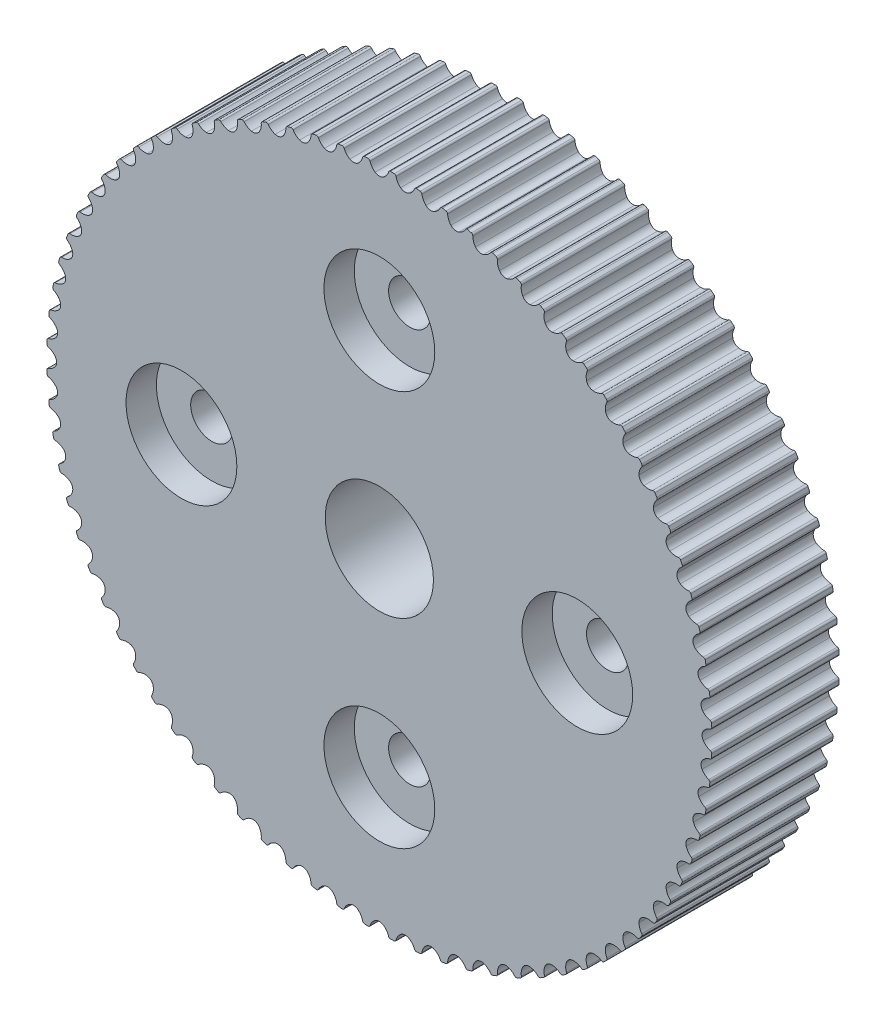
SolidWorks part; units mm, degrees
ref_plane "Front Plane" through (0, 0, 0) normal (0, 0, 1) x (1, 0, 0)
ref_plane "Top Plane" through (0, 0, 0) normal (0, 1, 0) x (1, 0, 0)
ref_plane "Right Plane" through (0, 0, 0) normal (1, 0, 0) x (0, 0, -1)
sketch "Sketch1" plane through (0, 0, 0) normal (0, 0, 1) x (1, 0, 0)
  line L3 (0, 25.2095) -> (1.9984, 25.1302) construction
  line L4 (0, 0) -> (0, 24.4595) construction
  line L5 (0, 24.4595) -> (0, 25.741) construction
  line L15 (1.9984, 25.1302) -> (2.047, 25.741)
  line L16 (2.047, 25.741) -> (-2.047, 25.741)
  line L17 (0, 24.4595) -> (0.1538, 24.4595) construction
  line L18 (-1.9984, 25.1302) -> (-2.047, 25.741)
  circle A0 centre (0, 0) radius 25.4635 construction
  circle A1 centre (0, 0) radius 25.2095 construction
  circle A2 centre (0, 0) radius 24.9555 construction
  arc A10 (0.8513, 25.1951) -> (1.9984, 25.1302) centre (0, 0) cw
  arc A11 (-0.3168, 24.5588) -> (0.3168, 24.5588) centre (0, 25.0145) ccw
  arc A12 (0.3168, 24.5588) -> (0.7027, 25.0889) centre (-0.254, 25.3799) ccw
  arc A13 (0.7027, 25.0889) -> (0.8513, 25.1951) centre (0.8462, 25.0452) cw
  arc A14 (-0.8513, 25.1951) -> (-1.9984, 25.1302) centre (0, 0) ccw
  arc A15 (-0.7027, 25.0889) -> (-0.8513, 25.1951) centre (-0.8462, 25.0452) ccw
  arc A16 (-0.3168, 24.5588) -> (-0.7027, 25.0889) centre (0.254, 25.3799) cw
  point P11 (0, 25.4635)
  point P13 (0, 25.2095)
  point P14 (0, 24.9555)
  dimension "D2" = 0.2775
sketch "Sketch2" plane through (0, 0, 0) normal (1, 0, 0) x (0, 0, -1)
  line L0 (-9.525, 4.1) -> (9.525, 4.1)
  line L1 (-9.525, 4.1) -> (-9.525, 19.05)
  line L2 (-9.525, 19.05) -> (-0.125, 19.05)
  line L3 (-0.125, 19.05) -> (-0.125, 25.2095)
  line L9 (9.525, 25.2095) -> (9.525, 4.1)
  line L10 (-9.525, 0) -> (9.525, 0) construction
  line L16 (-0.125, 25.2095) -> (9.525, 25.2095)
  point P25 (9.525, 0)
  point P26 (-0.125, 0)
  dimension "OA" = 19.05
  dimension "Bore" = 8.2
  dimension "Hub Dia" = 38.1
  dimension "Outside Width" = 9.65
revolve "Revolve1" add sketch "Sketch2" angle 360 mid plane about L10
sketch "Sketch3" plane through (0, 0, 0) normal (0, 0, 1) x (1, 0, 0)
  line L3 (1.9984, 25.1302) -> (2.047, 25.741) construction
  line L4 (-1.9984, 25.1302) -> (-2.047, 25.741) construction
  line L5 (2.047, 25.741) -> (-2.047, 25.741) construction
  line L6 (1.9984, 25.1302) -> (2.047, 25.741)
  line L7 (-1.9984, 25.1302) -> (-2.047, 25.741)
  line L8 (2.047, 25.741) -> (-2.047, 25.741)
  arc A0 (1.9984, 25.1302) -> (0.8513, 25.1951) centre (0, 0) ccw construction
  arc A1 (0.8513, 25.1951) -> (0.7027, 25.0889) centre (0.8462, 25.0452) ccw construction
  arc A3 (0.3168, 24.5588) -> (0.7027, 25.0889) centre (-0.254, 25.3799) ccw construction
  arc A4 (-0.3168, 24.5588) -> (0.3168, 24.5588) centre (0, 25.0145) ccw construction
  arc A5 (-0.7027, 25.0889) -> (-0.3168, 24.5588) centre (0.254, 25.3799) ccw construction
  arc A6 (-0.7027, 25.0889) -> (-0.8513, 25.1951) centre (-0.8462, 25.0452) ccw construction
  arc A7 (-0.8513, 25.1951) -> (-1.9984, 25.1302) centre (0, 0) ccw construction
  arc A8 (1.9984, 25.1302) -> (0.8513, 25.1951) centre (0, 0) ccw
  arc A9 (0.8513, 25.1951) -> (0.7027, 25.0889) centre (0.8462, 25.0452) ccw
  arc A10 (0.3168, 24.5588) -> (0.7027, 25.0889) centre (-0.254, 25.3799) ccw
  arc A11 (-0.3168, 24.5588) -> (0.3168, 24.5588) centre (0, 25.0145) ccw
  arc A12 (-0.7027, 25.0889) -> (-0.3168, 24.5588) centre (0.254, 25.3799) ccw
  arc A13 (-0.7027, 25.0889) -> (-0.8513, 25.1951) centre (-0.8462, 25.0452) ccw
  arc A14 (-0.8513, 25.1951) -> (-1.9984, 25.1302) centre (0, 0) ccw
extrude "Cut-Extrude1" cut sketch "Sketch3" against normal through all from surface starting at face at (19.05, 0, 0.125)
pattern_circular "CirPattern1" count 80 over 360 about axis through (0, 0, 9.525) along (0, 0, 1) of "Cut-Extrude1"
sketch "Sketch4" plane through (0, 0, 0) normal (1, 0, 0) x (0, 0, -1)
  line L0 (-9.525, 0) -> (-0.125, 0) construction
  line L1 (-9.525, 19.05) -> (-9.525, -19.05) construction
  line L2 (-0.125, 19.05) -> (-0.125, -19.05) construction
  circle A0 centre (-4.825, 0) radius 2.0828
  dimension "D1" = 4.1656
extrude "Cut-Extrude2" cut sketch "Sketch4" along normal through all
ref_plane "Plane1" through (0, 0, 4.825) normal (0, 0, 1) x (1, 0, 0)
sketch "Sketch5" plane through (0, 0, 4.825) normal (0, 0, 1) x (1, 0, 0)
  line L0 (3.5316, -2.0828) -> (18.9358, -2.0828) construction
  line L1 (4.481, -2.0828) -> (18.5548, -2.0828)
  line L2 (18.9358, -1.7018) -> (18.9358, 0)
  line L3 (18.9358, 0) -> (4.1, 0) construction
  line L4 (4.1, -1.7018) -> (4.1, 0)
  line L5 (4.481, -2.0828) -> (4.1, -1.7018)
  line L6 (18.5548, -2.0828) -> (18.9358, -1.7018)
  line L13 (3.5316, -2.0828) -> (18.9358, -2.0828) construction
  line L23 (4.1, 0) -> (18.9358, 0)
  circle A0 centre (0, 0) radius 19.05 construction
  circle A1 centre (0, 0) radius 4.1 construction
  point P0 (4.1, -2.0828)
  point P3 (18.9358, -2.0828)
  point P4 (-19.05, 0)
  point P6 (-4.1, 0)
ref_axis "Center Axis 1" through (0, 0, -9.525) along (0, 0, 1)
ref_plane "Contact Plane 1" through (0, 0, 9.525) normal (0, 0, 1) x (1, 0, 0)
ref_plane "Contact Plane 2" through (0, 0, -9.525) normal (0, 0, -1) x (-1, 0, 0)
sketch "Sketch6" plane through (0, 0, 9.525) normal (0, 0, 1) x (1, 0, 0)
  line L1 (6.985, 6.35) -> (13.335, 6.35)
  line L2 (6.985, 6.35) -> (6.985, -6.35)
  line L3 (6.985, -6.35) -> (13.335, -6.35)
  line L4 (13.335, 6.35) -> (13.335, -6.35)
  line L5 (6.985, 6.35) -> (13.335, -6.35) construction
  line L6 (6.985, -6.35) -> (13.335, 6.35) construction
  point P4 (10.16, 0)
  dimension "D1" = 6.35
  dimension "D2" = 12.7
  dimension "D3" = 10.16
sketch "Sketch7" plane through (0, 0, 0.125) normal (0, 0, 1) x (1, 0, 0)
  circle A0 centre (0, 0) radius 19.05 construction
  circle A1 centre (0, 0) radius 19.05
extrude "Cut-Extrude5" cut sketch "Sketch7" along normal up to surface (9.4 mm away) up to face at (4.1, 0, 9.525)
hole_wizard "CBORE for M3 Hex Head Machine Screw1" positions "Sketch8" profile "Sketch9" counterbore size "M3" standard "ANSI Metric" end condition through all
sketch "Sketch8" plane through (0, 0, 0.125) normal (0, 0, 1) x (1, 0, 0)
  line L0 (-15, 0) -> (15, 0) construction
  line L2 (0, -15) -> (0, 15) construction
  circle A0 centre (0, 0) radius 15
  point P0 (0, -15)
  point P2 (0, 15)
  point P4 (-15, 0)
  point P6 (15, 0)
  dimension "D1" = 30
sketch "Sketch9" plane through (0, -15, 0.125) normal (1, 0, 0) x (0, -1, 0)
  line L0 (0, 0) -> (0, 9.65)
  line L1 (0, 9.65) -> (1.6, 9.65)
  line L3 (1.6, 9.65) -> (1.6, 2.3)
  line L4 (1.6, 2.3) -> (4.2, 2.3)
  line L5 (4.2, 2.3) -> (4.2, 0)
  line L7 (4.2, 0) -> (0, 0)
  line L11 (0, -6.35) -> (0, 107.95) construction
  dimension "Thru Hole Dia." = 3.2
  dimension "Thru Hole Depth" = 9.65
  dimension "C'Bore Dia." = 8.4
  dimension "C'Bore Depth" = 2.3
equation "\"D2@Sketch1\" = \"R3@Sketch1\"/2"
